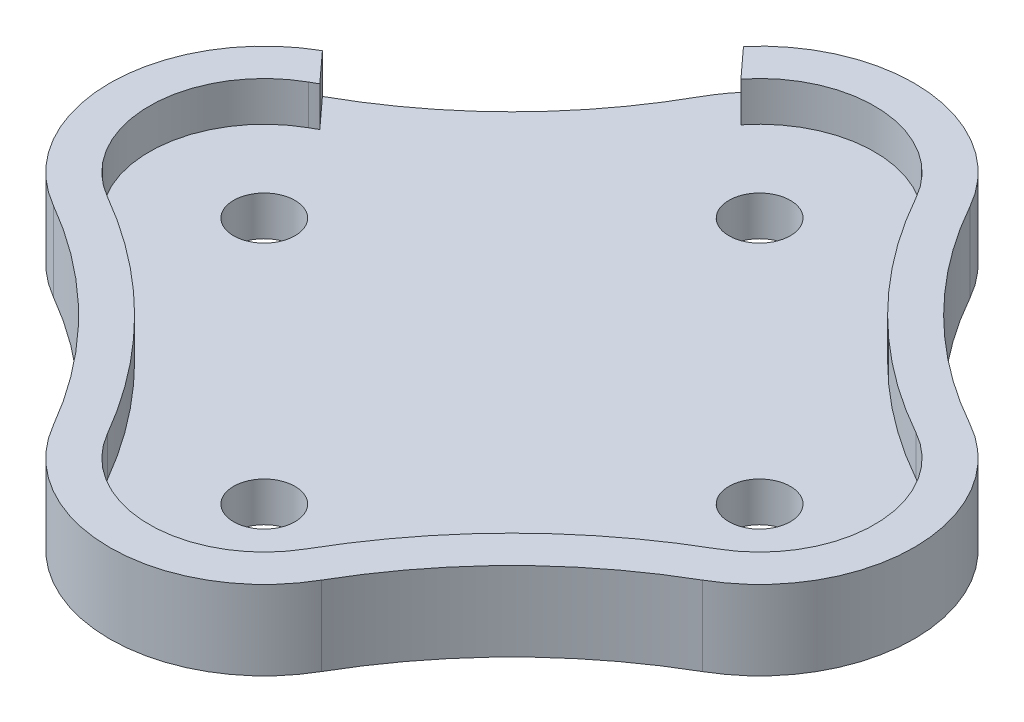
SolidWorks part; units mm, degrees
ref_plane "前视基准面" through (0, 0, 0) normal (0, 0, 1) x (1, 0, 0)
ref_plane "上视基准面" through (0, 0, 0) normal (0, 1, 0) x (1, 0, 0)
ref_plane "右视基准面" through (0, 0, 0) normal (1, 0, 0) x (0, 0, -1)
sketch "草图1" plane through (0, 0, 0) normal (0, 1, 0) x (1, 0, 0)
  line L0 (6, 0) -> (-6, 0) construction
  line L2 (0, 1014.7295) -> (0, 11.1147) construction
  line L6 (0, 18.3) -> (0, -7.5) construction
  circle A0 centre (-12.5, 0) radius 1.55
  circle A1 centre (0, 12.5) radius 1.55
  circle A2 centre (12.5, 0) radius 1.55
  circle A3 centre (0, -12.5) radius 1.55
  arc A4 (5.067, 15.3224) -> (-5.067, 15.3224) centre (0, 12.5) ccw
  arc A5 (-15.3224, 5.067) -> (-15.39, -5.0287) centre (-12.5, 0) ccw
  arc A6 (15.3224, 5.067) -> (15.39, -5.0287) centre (12.5, 0) cw
  arc A7 (5.0287, -15.39) -> (-5.0287, -15.39) centre (0, -12.5) cw
  arc A8 (5.067, 15.3224) -> (15.3224, 5.067) centre (28.2178, 28.2178) ccw
  arc A10 (-5.067, 15.3224) -> (-15.3224, 5.067) centre (-28.2178, 28.2178) cw
  arc A11 (-15.39, -5.0287) -> (-5.0287, -15.39) centre (-29.3918, -29.3918) cw
  arc A12 (15.39, -5.0287) -> (5.0287, -15.39) centre (29.3918, -29.3918) ccw
  arc A13 (-6.8142, 16.2956) -> (-16.2956, 6.8142) centre (-28.2178, 28.2178) cw
  arc A14 (-16.2956, 6.8142) -> (-16.3866, -6.7627) centre (-12.5, 0) ccw
  arc A15 (-16.3866, -6.7627) -> (-6.7627, -16.3866) centre (-29.3918, -29.3918) cw
  arc A16 (6.7627, -16.3866) -> (-6.7627, -16.3866) centre (0, -12.5) cw
  arc A17 (16.3866, -6.7627) -> (6.7627, -16.3866) centre (29.3918, -29.3918) ccw
  arc A18 (16.2956, 6.8142) -> (16.3866, -6.7627) centre (12.5, 0) cw
  arc A19 (6.8142, 16.2956) -> (16.2956, 6.8142) centre (28.2178, 28.2178) ccw
  arc A20 (6.8142, 16.2956) -> (-6.8142, 16.2956) centre (0, 12.5) ccw
  dimension "D1" = 5.8
  dimension "D4" = 5.8
  dimension "D5" = 26.5
  dimension "D6" = 28.1
  dimension "D2" = 25
  dimension "D3" = 25
  dimension "D8" = 2
extrude "凸台-拉伸1" add sketch "草图1" along normal blind 4 contours A19 A20 A13 A14 A15 A16 A17 A18 A6 A12 A7 A11 A5 A10 A4 A8 region at (0, 0, -19.7258)
extrude "凸台-拉伸2" add sketch "草图1<3>" along normal blind 2 contours A12 A6 A8 A4 A10 A5 A11 A7 A3 A2 A1 A0 region at (0, 0, 0.0153)
sketch "草图1<3>" plane through (0, 0, 0) normal (0, 1, 0) x (1, 0, 0) same geometry as "草图1"
sketch "草图2" plane through (0, 4, 0) normal (0, 1, 0) x (1, 0, 0)
  line L0 (0, 0) -> (-9.8239, 10.7595) construction
  line L1 (-17.6755, 8.2357) -> (-13.6299, 3.8048)
  line L2 (0, 0) -> (-9.2031, -8.4028) construction
  line L3 (-13.6299, 3.8048) -> (-2.5526, 13.9188)
  line L4 (-2.5526, 13.9188) -> (-6.5982, 18.3498)
  line L5 (-6.5982, 18.3498) -> (-17.6755, 8.2357)
  dimension "D1" = 15
  dimension "D2" = 6
  dimension "D3" = 12
extrude "切除-拉伸1" cut sketch "草图2" against normal up to surface (2 mm away) up to face at (0, 2, 0.0009)
